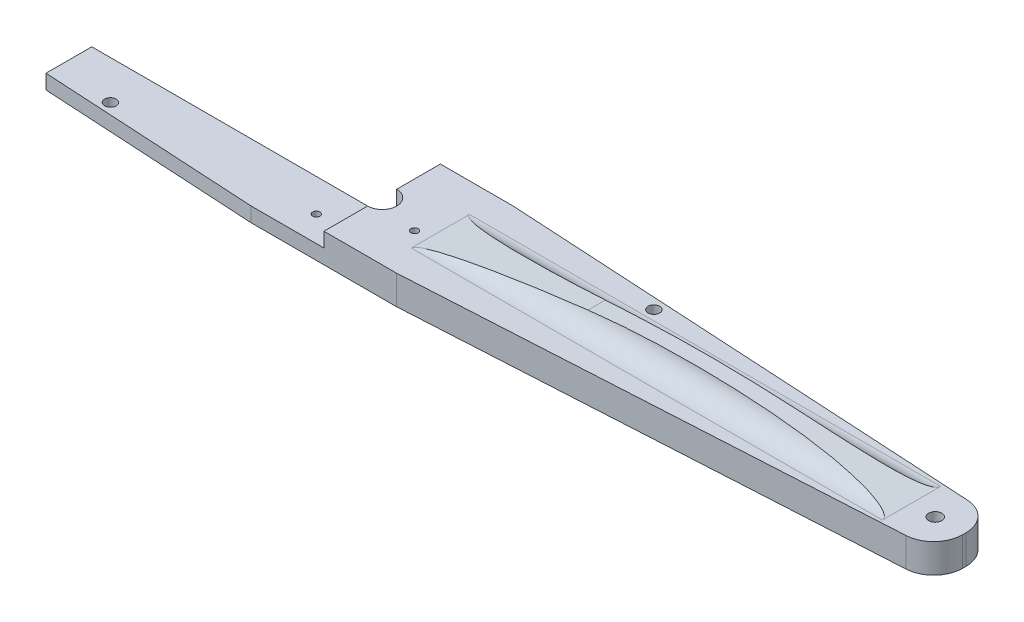
SolidWorks part; units mm, degrees
material "Polylactic Acid (PLA)"
ref_plane "Front Plane" through (0, 0, 0) normal (0, 0, 1) x (1, 0, 0)
ref_plane "Top Plane" through (0, 0, 0) normal (0, 1, 0) x (1, 0, 0)
ref_plane "Right Plane" through (0, 0, 0) normal (1, 0, 0) x (0, 0, -1)
sketch "Sketch2" plane through (0, 0, 0) normal (0, 0, 1) x (1, 0, 0)
  line L0 (0, 0) -> (200, 0)
  line L1 (55, 0) -> (-55, 0) construction
  line L2 (200, 0) -> (200, 10)
  line L3 (200, 10) -> (-200, 10)
  line L4 (-200, 10) -> (-200, 0)
  line L5 (-200, 0) -> (0, 0)
  line L6 (0, -55) -> (0, 55) construction
  dimension "D1" = 10
  dimension "D2" = 200
  dimension "D3" = 200
extrude "Boss-Extrude1" add sketch "Sketch2" along normal mid plane 40
sketch "Sketch3" plane through (0, 10, 0) normal (0, 1, 0) x (1, 0, 0)
  line L1 (0, 0) -> (-5.567, 9.6423) construction
  line L2 (0, 0) -> (16, 0) construction
  line L3 (-200, -20) -> (-200, 20) construction
  line L4 (0, -55) -> (0, 55) construction
  circle A0 centre (-4, 15.4919) radius 1.25
  circle A1 centre (15.4164, -4.2819) radius 1.25
  circle A2 centre (-11.4164, -11.2101) radius 1.25
  circle A3 centre (0, 0) radius 5
  circle A4 centre (-190, 0) radius 2.25
  circle A5 centre (190, 0) radius 2.25
  point P10 (0, 0)
  dimension "D1" = 3
  dimension "D3" = 10
  dimension "D4" = 16
  dimension "D2" = 120
  dimension "D5" = 4
extrude "Cut-Extrude1" cut sketch "Sketch3" against normal blind 40
sketch "Sketch4" plane through (0, 10, 0) normal (0, 1, 0) x (1, 0, 0)
  line L0 (-55, 0) -> (55, 0) construction
  line L1 (-205.6824, 30.2666) -> (-25, 30.2666)
  line L2 (-205.6824, 30.2666) -> (-205.6824, 10)
  line L3 (-205.6824, 10) -> (-200, 10)
  line L4 (-25, 30.2666) -> (-25, 20)
  line L5 (-200, -20) -> (-200, 20) construction
  line L6 (-25, 20) -> (-200, 10)
  line L7 (200, 20) -> (-200, 20) construction
  dimension "D1" = 10
  dimension "D2" = 175
extrude "Cut-Extrude2" cut sketch "Sketch4" against normal blind 40
mirror "Mirror1" about plane through (0, 0, 0) normal (1, 0, 0) of "Cut-Extrude2"
mirror "Mirror2" about plane through (0, 0, 0) normal (0, 0, 1) of "Mirror1", "Cut-Extrude2"
sketch "Sketch5" plane through (0, 0, 0) normal (0, 0, 1) x (1, 0, 0)
  line L1 (-181.849, 10) -> (-20, 10)
  line L2 (-130, 20) -> (-20, 10)
  line L5 (-200, 10) -> (-25, 10) construction
  line L6 (-181.849, 10) -> (-130, 20)
extrude "Boss-Extrude3" add sketch "Sketch5" along normal mid plane 5
mirror "Mirror3" about plane through (0, 0, 0) normal (1, 0, 0) of "Boss-Extrude3"
sketch "Sketch6" plane through (0, 0, 0) normal (0, 0, 1) x (1, 0, 0)
  line L1 (-203.4298, 23.9575) -> (-99.7587, 23.9575)
  line L2 (-203.4298, 23.9575) -> (-203.4298, 0)
  line L3 (-203.4298, 0) -> (-99.7587, 0)
  line L4 (-99.7587, 23.9575) -> (-99.7587, 0)
extrude "Cut-Extrude3" cut sketch "Sketch6" against normal mid plane 50
sketch "Sketch7" plane through (0, 0, 0) normal (0, 0, 1) x (1, 0, 0)
  line L0 (0, -11) -> (0, 11) construction
  line L1 (-105.2125, 24.7655) -> (0, 24.7655)
  line L2 (-105.2125, 24.7655) -> (-105.2125, 5)
  line L3 (-105.2125, 5) -> (0, 5)
  line L4 (0, 24.7655) -> (0, 5)
  line L5 (22, 0) -> (-22, 0) construction
  dimension "D1" = 5
extrude "Cut-Extrude4" cut sketch "Sketch7" against normal mid plane 50
sketch "Sketch8" plane through (0, 0, 0) normal (0, 0, 1) x (1, 0, 0)
  line L1 (-102.8468, 8.5613) -> (0, 8.5613)
  line L2 (-102.8468, 8.5613) -> (-102.8468, -9.8409)
  line L3 (-102.8468, -9.8409) -> (0, -9.8409)
  line L4 (0, 8.5613) -> (0, -9.8409)
extrude "Cut-Extrude5" cut sketch "Sketch8" against normal blind 50
sketch "Sketch9" plane through (0, 0, 0) normal (0, 0, 1) x (1, 0, 0)
  line L0 (0, -11) -> (0, 11) construction
  line L1 (0, 5) -> (100, 5)
  line L2 (0, 5) -> (0, -4.3794)
  line L3 (0, -4.3794) -> (100, -4.3794)
  line L4 (100, 5) -> (100, -4.3794)
  line L5 (-25, 5) -> (0, 5) construction
extrude "Cut-Extrude6" cut sketch "Sketch9" against normal blind 50
fillet "Fillet2" radius 10 2 edges at (200, 5, -10) (200, 5, 10)
fillet "Fillet3" radius 400 1 edges at (130, 20, 0)
fillet "Fillet4" radius 7.5 2 edges at (100.9245, 10, 2.5) (100.9245, 10, -2.5)
sketch "Sketch10" plane through (0, 10, 0) normal (0, 1, 0) x (1, 0, 0)
  line L0 (0, 20) -> (0, 5) construction
  line L1 (190.5705, 10.5388) -> (25, 20) construction
  line L2 (-99.7587, -15.7281) -> (-25, -20) construction
  line L3 (0, -5) -> (0, -20) construction
  circle A0 centre (80, 13.3514) radius 2
  circle A1 centre (-80, -13.3514) radius 2
  dimension "D1" = 80
  dimension "D2" = 3.5
  dimension "D3" = 4
  dimension "D6" = 4
  dimension "D4" = 3.5
  dimension "D5" = 80
extrude "Cut-Extrude7" cut sketch "Sketch10" against normal blind 10
